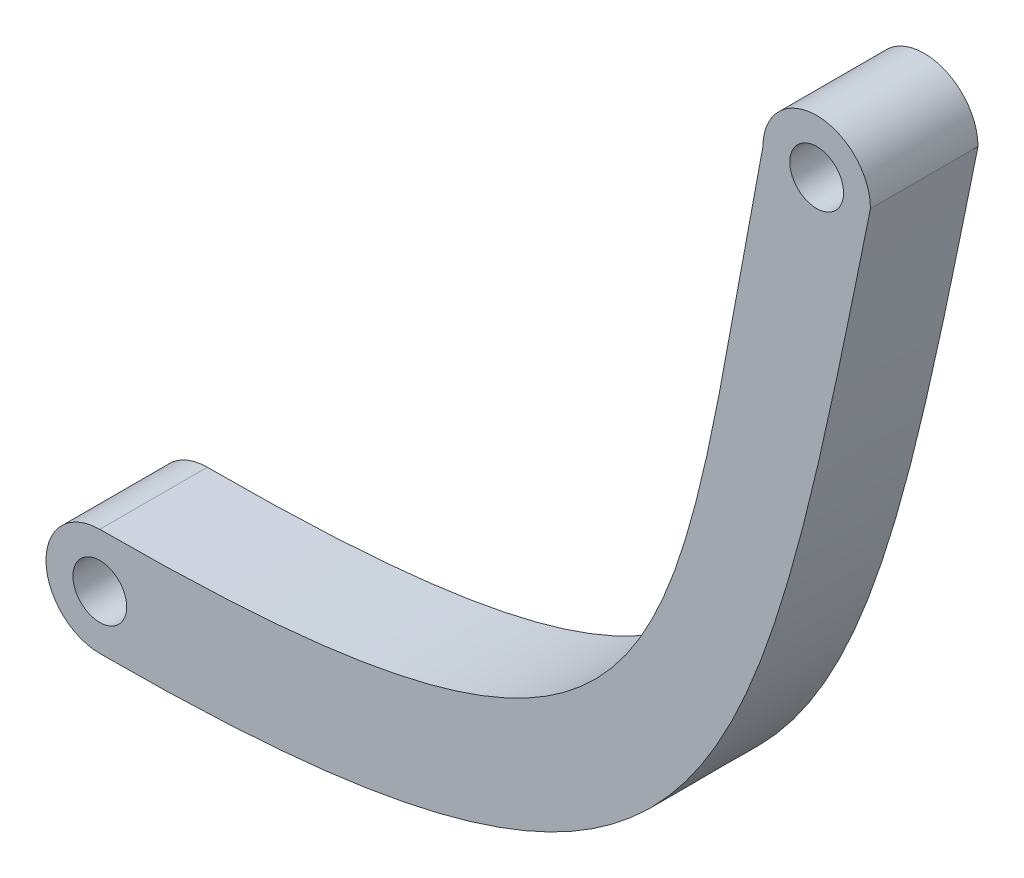
SolidWorks part; units mm, degrees
ref_plane "Plan de face" through (0, 0, 0) normal (0, 0, 1) x (1, 0, 0)
ref_plane "Plan de dessus" through (0, 0, 0) normal (0, 1, 0) x (1, 0, 0)
ref_plane "Plan de droite" through (0, 0, 0) normal (1, 0, 0) x (0, 0, -1)
sketch "Esquisse1" plane through (0, 0, 0) normal (0, 0, 1) x (1, 0, 0)
  line L0 (0, 3) -> (0, -3) construction
  line L1 (43, 40) -> (37, 40) construction
  circle A0 centre (0, 0) radius 1.5
  circle A1 centre (40, 40) radius 1.5
  arc A2 (0, 3) -> (0, -3) centre (0, 0) ccw
  arc A3 (37, 40) -> (43, 40) centre (40, 40) cw
  spline S0 degree 3 poles (0, 3) (33.3333, 3) (31.6647, 12.3591) (37, 40) knots 0 0 0 0 1 1 1 1
  spline S1 degree 3 poles (0, -3) (34.5474, -3) (36.3595, 7.3348) (43, 40) knots 0 0 0 0 1 1 1 1
  dimension "D1" = 3
  dimension "D4" = 100
  dimension "D7" = 100
  dimension "D2" = 6
  dimension "D3" = 6
extrude "Boss.-Extru.1" add sketch "Esquisse1" along normal blind 3 and the other way blind 3 contours S1 A3 S0 A2 | A0 | A1
